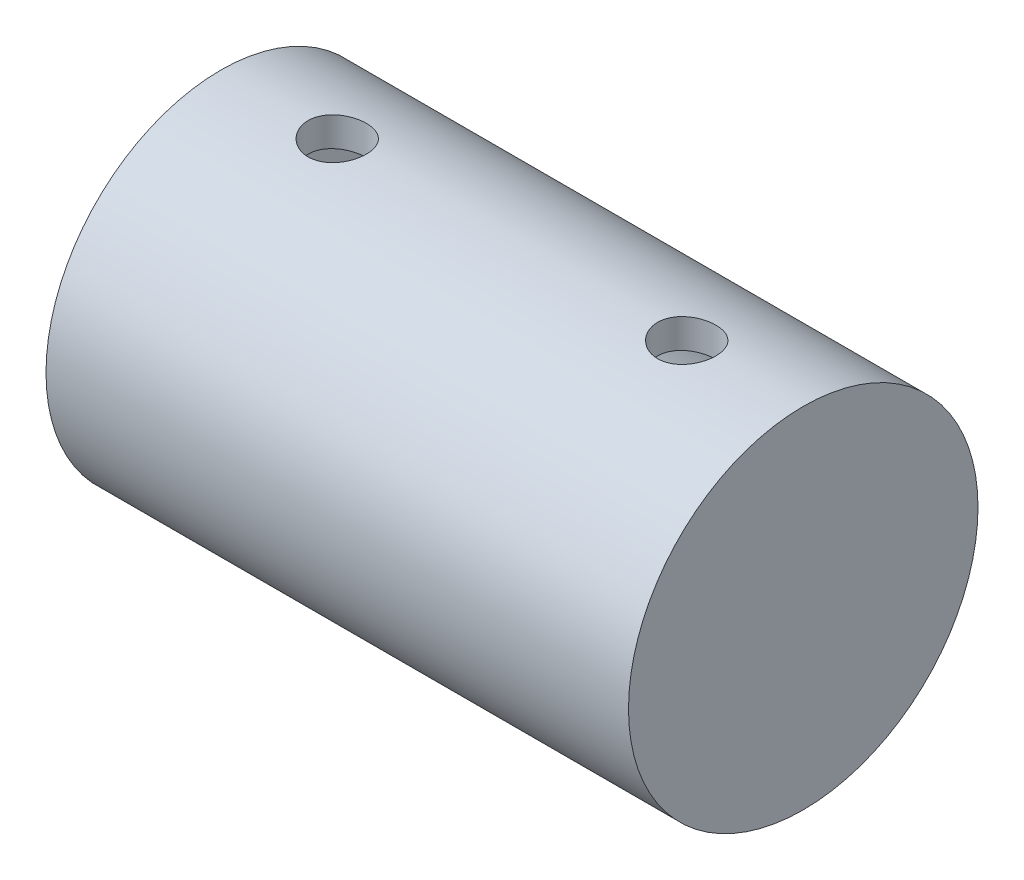
SolidWorks part; units mm, degrees
ref_plane "Front Plane" through (0, 0, 0) normal (0, 0, 1) x (1, 0, 0)
ref_plane "Top Plane" through (0, 0, 0) normal (0, 1, 0) x (1, 0, 0)
ref_plane "Right Plane" through (0, 0, 0) normal (1, 0, 0) x (0, 0, -1)
sketch "Sketch1" plane through (0, 0, 0) normal (1, 0, 0) x (0, 0, -1)
  circle A0 centre (0, 0) radius 15
  circle A1 centre (0, 0) radius 12.5
  dimension "D1" = 25
  dimension "D2" = 30
extrude "Boss-Extrude1" add sketch "Sketch1" along normal mid plane 50
extrude "Boss-Extrude2" add sketch "Sketch1<2>" along normal blind 5 from offset 20 contours A1
sketch "Sketch1<2>" plane through (0, 0, 0) normal (1, 0, 0) x (0, 0, -1) same geometry as "Sketch1"
extrude "Boss-Extrude3" add sketch "Sketch1<3>" against normal blind 5 from offset 20 contours A1 offset against normal yes
sketch "Sketch1<3>" plane through (0, 0, 0) normal (1, 0, 0) x (0, 0, -1) same geometry as "Sketch1"
sketch "Sketch2" plane through (0, 0, 0) normal (0, 1, 0) x (1, 0, 0)
  circle A0 centre (-15, 0) radius 2.5
  circle A1 centre (15, 0) radius 2.5
  dimension "D1" = 5
  dimension "D2" = 15
  dimension "D3" = 15
extrude "Cut-Extrude1" cut sketch "Sketch2" along normal through all
